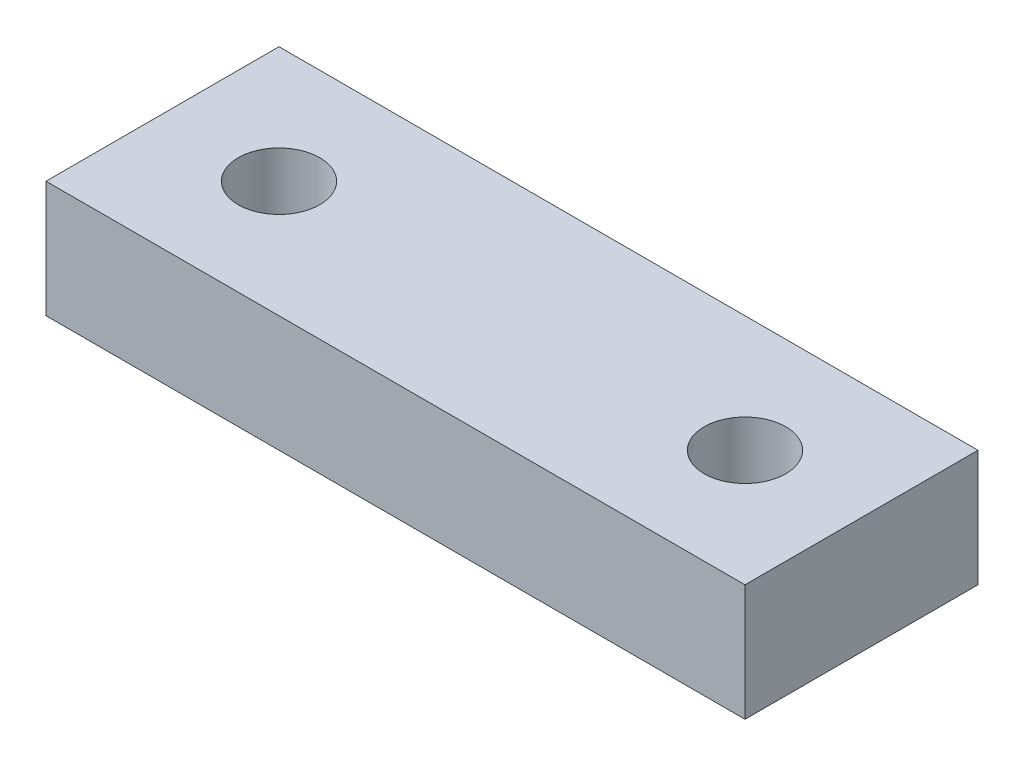
SolidWorks part; units mm, degrees
material "Lega 1060"
ref_plane "Piano frontale" through (0, 0, 0) normal (0, 0, 1) x (1, 0, 0)
ref_plane "Piano superiore" through (0, 0, 0) normal (0, 1, 0) x (1, 0, 0)
ref_plane "Piano destro" through (0, 0, 0) normal (1, 0, 0) x (0, 0, -1)
sketch "Schizzo1" plane through (0, 0, 0) normal (0, 0, 1) x (1, 0, 0)
  line L4 (-15, 0) -> (15, 0)
  line L5 (0, -4.2112) -> (0, 9.1781) construction
  line L7 (15, 0) -> (15, 5)
  line L8 (15, 5) -> (-15, 5)
  line L9 (-15, 5) -> (-15, 0)
  dimension "D1" = 5
  dimension "D4" = 30
extrude "Estrusione-Estrusione1" add sketch "Schizzo1" along normal blind 10
sketch "Schizzo2" plane through (0, 5, 0) normal (0, 1, 0) x (1, 0, 0)
  line L0 (-12.7999, -5) -> (12.1785, -5) construction
  line L1 (15, -10) -> (-15, -10) construction
  line L2 (15, 0) -> (-15, 0) construction
  line L3 (-15, -10) -> (-15, 0) construction
  line L4 (15, -10) -> (15, 0) construction
  point P0 (-10, -5)
  point P1 (10, -5)
  dimension "D1" = 5
  dimension "D2" = 5
hole_wizard "Foro Ø3.5 (3.5)-1" positions "Schizzo4" profile "Schizzo3" hole size "Ø3.5" standard "ISO" end condition through all
sketch "Schizzo4" plane through (0, 5, 0) normal (0, 1, 0) x (1, 0, 0)
  point P0 (-10, -5)
  point P8 (10, -5)
sketch "Schizzo3" plane through (-10, 5, 5) normal (1, 0, 0) x (0, 0, 1)
  line L0 (0, 0) -> (0, 5)
  line L1 (0, 5) -> (1.75, 5)
  line L2 (1.75, 5) -> (1.75, 0)
  line L5 (1.75, 0) -> (0, 0)
  line L11 (0, -6.35) -> (0, 107.95) construction
  dimension "Thru Hole Dia." = 3.5
  dimension "Thru Hole Depth" = 5
